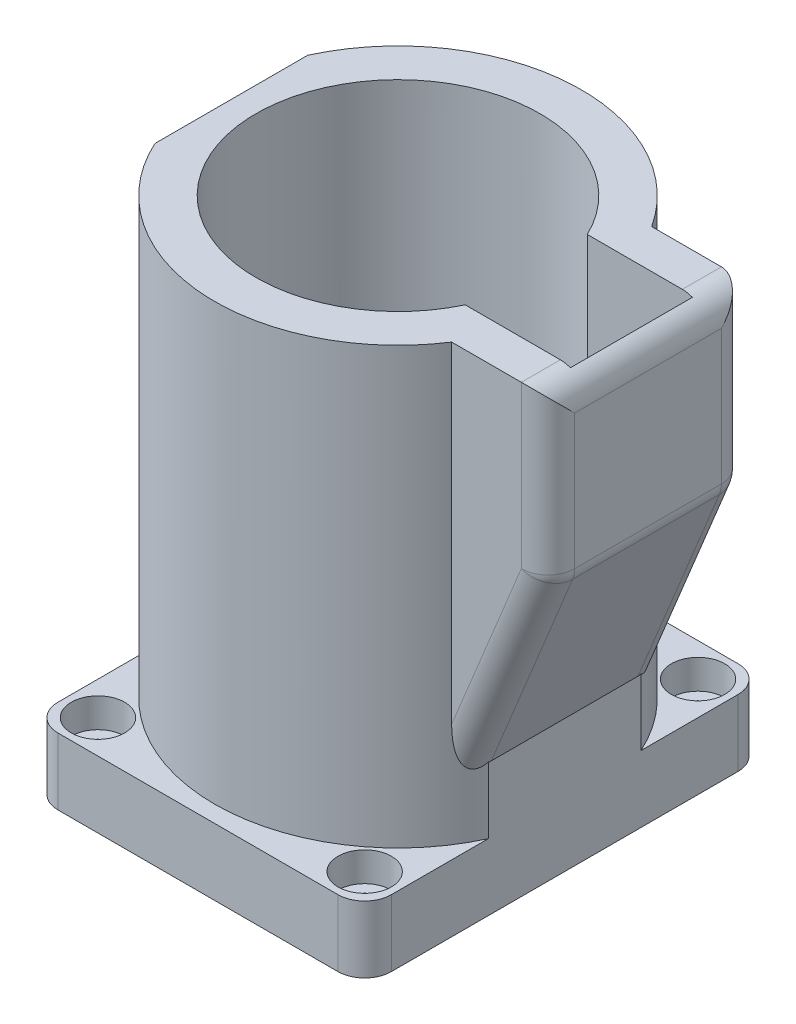
SolidWorks part; units mm, degrees
ref_plane "Plan de face" through (0, 0, 0) normal (0, 0, 1) x (1, 0, 0)
ref_plane "Plan de dessus" through (0, 0, 0) normal (0, 1, 0) x (1, 0, 0)
ref_plane "Plan de droite" through (0, 0, 0) normal (1, 0, 0) x (0, 0, -1)
sketch "Esquisse1" plane through (0, 0, 0) normal (0, 1, 0) x (1, 0, 0)
  line L0 (0, 60) -> (50, 0) construction
  line L1 (0, 0) -> (50, 0)
  line L2 (0, 0) -> (0, 60)
  line L3 (0, 60) -> (50, 60)
  line L4 (50, 0) -> (50, 60)
  circle A0 centre (25, 30) radius 14.5
  dimension "D3" = 29
  dimension "D1" = 60
  dimension "D2" = 50
extrude "Boss.-Extru.1" add sketch "Esquisse1" along normal blind 10
sketch "Esquisse2" plane through (0, 10, 0) normal (0, 1, 0) x (1, 0, 0)
  line L4 (0, 60) -> (0, 0)
  line L5 (0, 0) -> (50, 0)
  line L6 (50, 0) -> (50, 60)
  line L7 (50, 60) -> (0, 60)
  line L8 (0, 60) -> (0, 0)
  line L9 (0, 0) -> (50, 0)
  line L10 (50, 0) -> (50, 60)
  line L11 (50, 60) -> (0, 60)
  circle A0 centre (25, 30) radius 14.5 construction
  circle A1 centre (25, 30) radius 14.5
  circle A3 centre (25, 30) radius 21.3
  circle A4 centre (25, 30) radius 27.5
  dimension "D2" = 42.6
  dimension "D3" = 55
  dimension "D1" = 0
extrude "Boss.-Extru.2" add sketch "Esquisse2" along normal blind 65.3 contours L10 A4 L8 A3 region at (25, 10, -56.7567)
sketch "Esquisse3" plane through (0, 75.3, 0) normal (0, 1, 0) x (1, 0, 0)
  line L6 (42.5, 15) -> (62.5, 15)
  line L8 (42.5, 15) -> (42.5, 45)
  line L9 (42.5, 45) -> (62.5, 45)
  line L11 (62.5, 15) -> (62.5, 45)
  line L12 (42.5, 15) -> (62.5, 45) construction
  line L13 (42.5, 45) -> (62.5, 15) construction
  arc A3 (0, 18.5436) -> (50, 18.5436) centre (25, 30) ccw construction
  arc A4 (50, 41.4564) -> (0, 41.4564) centre (25, 30) ccw construction
  arc A5 (0, 18.5436) -> (50, 18.5436) centre (25, 30) ccw
  arc A6 (50, 41.4564) -> (0, 41.4564) centre (25, 30) ccw
  circle A7 centre (25, 30) radius 27.5
  point P7 (52.5, 30)
  line M3 (50, 18.5436) -> (50, 41.4564)
  arc M4 (50, 41.4564) -> (0, 41.4564) centre (25, 30) ccw
  arc M6 (0, 18.5436) -> (50, 18.5436) centre (25, 30) ccw
  dimension "D1" = 30
  dimension "D2" = 20
extrude "Boss.-Extru.3" add sketch "Esquisse3" against normal blind 25 contours A7 L6 L11 L9 M6 M4 | A7 M3 region at (56.709, 75.3, -30) region at (51.004, 75.3, -30)
sketch "Esquisse4" plane through (0, 75.3, -75.3) normal (0, -1, 0) x (1, 0, 0)
  line L1 (-10, 36.15) -> (60, 36.15)
  line L2 (-10, 36.15) -> (-10, 54.45)
  line L3 (-10, 54.45) -> (60, 54.45)
  line L4 (60, 36.15) -> (60, 54.45)
  line L5 (-10, 36.15) -> (60, 54.45) construction
  line L6 (-10, 54.45) -> (60, 36.15) construction
  circle A1 centre (25, 45.3) radius 21.1
  circle A2 centre (25, 45.3) radius 21.3 construction
  circle A3 centre (25, 45.3) radius 21.3
  circle M15 centre (25, 45.3) radius 21.3
  dimension "D1" = 18.3
  dimension "D2" = 70
extrude "Enlèv. mat.-Extru.1" cut sketch "Esquisse4" along normal blind 22 contours L4 L1 L3 M15 region at (52.7997, 75.3, -30)
sketch "Esquisse5" plane through (0, 10, 0) normal (0, 1, 0) x (1, 0, 0)
  line L0 (50, 0) -> (50, 18.5436) construction
  line L1 (5, 55) -> (45, 55)
  line L2 (5, 55) -> (5, 5)
  line L3 (5, 5) -> (45, 5)
  line L4 (45, 55) -> (45, 5)
  line L5 (5, 55) -> (45, 5) construction
  line L6 (5, 5) -> (45, 55) construction
  line L7 (0, 0) -> (50, 0) construction
  circle A0 centre (25, 30) radius 14.5 construction
  circle A1 centre (25, 30) radius 14.5
  dimension "D1" = 5
  dimension "D2" = 5
hole_wizard "Chambrage pour vis à six pans creux M41" positions "Esquisse3D2" profile "Esquisse7" counterbore size "M4" standard "ISO" end condition through all
sketch3d "Esquisse3D2"
  point P0 (5, 10, -55)
  point P3 (45, 10, -55)
  point P6 (45, 10, -5)
  point P9 (5, 10, -5)
sketch "Esquisse7" plane through (5, 10, -55) normal (1, 0, 0) x (0, 0, 1)
  line L0 (0, 0) -> (0, 10)
  line L1 (0, 10) -> (2.25, 10)
  line L3 (2.25, 10) -> (2.25, 4.4)
  line L4 (2.25, 4.4) -> (4, 4.4)
  line L5 (4, 4.4) -> (4, 0)
  line L7 (4, 0) -> (0, 0)
  line L11 (0, -6.35) -> (0, 107.95) construction
  dimension "Diamètre du perçage jusqu'au prochain" = 4.5
  dimension "Profondeur du perçage jusqu'au prochain" = 10
  dimension "Diamètre du chambrage" = 8
  dimension "Profondeur du chambrage" = 4.4
sketch "Esquisse8" plane through (0, 0, 0) normal (0, 1, 0) x (1, 0, 0)
  circle A0 centre (25, 30) radius 17.5
  circle A1 centre (25, 30) radius 21.3
  circle A2 centre (25, 30) radius 21.3
  point P1 (25, 47.5)
  point P5 (42.5, 30)
  point P6 (25, 12.5)
  point P7 (7.5, 30)
  dimension "D2" = 35
  dimension "D1" = 0
hole_wizard "Chambrage pour vis à six pans creux M42" positions "Esquisse3D4" profile "Esquisse10" counterbore size "M4" standard "ISO" end condition through all
sketch3d "Esquisse3D4"
  point P0 (25, 0, -12.5)
  point P3 (42.5, 0, -30)
  point P6 (25, 0, -47.5)
  point P9 (7.5, 0, -30)
sketch "Esquisse10" plane through (25, 0, -12.5) normal (1, 0, 0) x (0, 0, -1)
  line L0 (0, 0) -> (0, 75.3)
  line L1 (0, 75.3) -> (2.4, 75.3)
  line L3 (2.4, 75.3) -> (2.4, 4.4)
  line L4 (2.4, 4.4) -> (4, 4.4)
  line L5 (4, 4.4) -> (4, 0)
  line L7 (4, 0) -> (0, 0)
  line L11 (0, -6.35) -> (0, 107.95) construction
  dimension "Diamètre du perçage jusqu'au prochain" = 4.8
  dimension "Profondeur du perçage jusqu'au prochain" = 75.3
  dimension "Diamètre du chambrage" = 8
  dimension "Profondeur du chambrage" = 4.4
sketch "Esquisse11" plane through (0, 0, -15) normal (0, 0, 1) x (1, 0, 0)
  line L0 (62.5, 50.3) -> (48.0489, 15.1348)
  line L1 (48.0489, 50.3) -> (62.5, 50.3)
  line L2 (48.0489, 50.3) -> (48.0489, 15.1348)
  line L3 (48.0489, 15.1348) -> (62.5, 15.1348)
  line L4 (62.5, 50.3) -> (62.5, 15.1348)
  line L9 (62.5, 75.3) -> (48.0489, 75.3)
  line L10 (48.0489, 75.3) -> (48.0489, 50.3)
  line L11 (48.0489, 50.3) -> (62.5, 50.3)
  line L12 (62.5, 50.3) -> (62.5, 75.3)
  line L13 (62.5, 75.3) -> (48.0489, 75.3)
  line L14 (48.0489, 75.3) -> (48.0489, 50.3)
  line L15 (48.0489, 50.3) -> (62.5, 50.3)
  line L16 (62.5, 50.3) -> (62.5, 75.3)
  line M7 (48.0489, 50.3) -> (62.5, 50.3)
  dimension "D1" = 0
extrude "Boss.-Extru.4" add sketch "Esquisse11" against normal blind 30 contours L2 L0 M7 region at (52.8659, 38.5783, -15)
fillet "Congé1" radius 4 4 edges at (50, 5, -60) (0, 5, -60) (50, 5, 0) (0, 5, 0)
fillet "Congé2" radius 4 6 edges at (62.5, 62.8, -45) (62.5, 50.3, -30) (62.5, 62.8, -15) (62.5, 75.3, -30) (55.2744, 32.7174, -45) (55.2744, 32.7174, -15)
